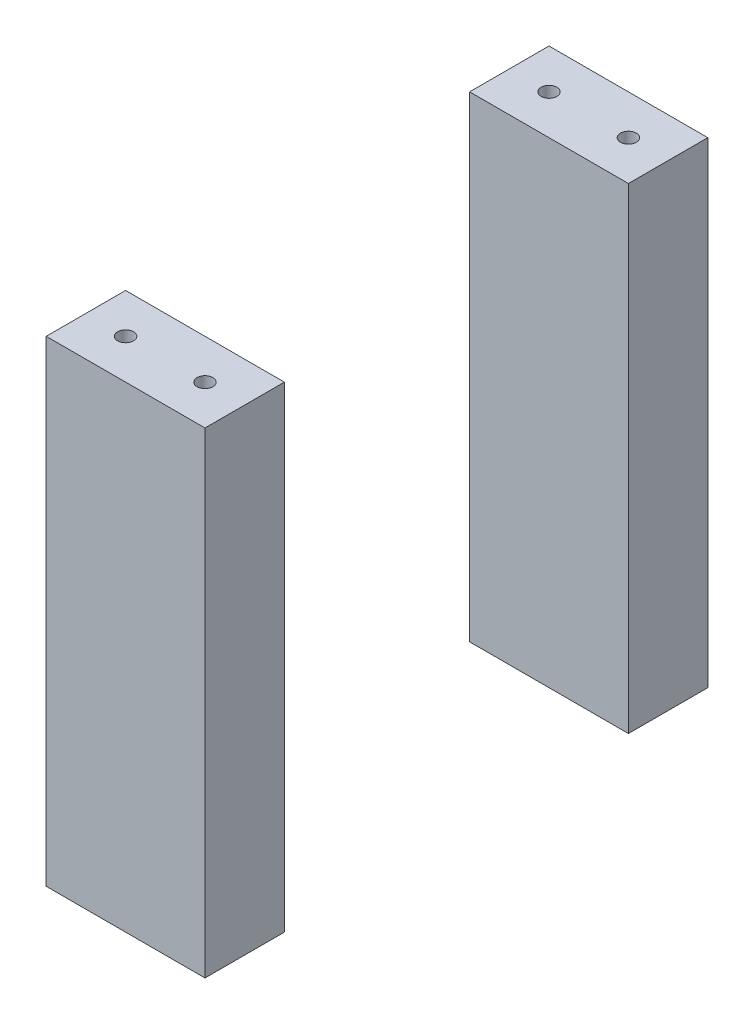
SolidWorks part; units mm, degrees
ref_plane "Ebene vorne" through (0, 0, 0) normal (0, 0, 1) x (1, 0, 0)
ref_plane "Ebene oben" through (0, 0, 0) normal (0, 1, 0) x (1, 0, 0)
ref_plane "Ebene rechts" through (0, 0, 0) normal (1, 0, 0) x (0, 0, -1)
sketch "OutlineBase" plane through (0, 0, 0) normal (0, 1, 0) x (1, 0, 0)
  line L0 (0, -95) -> (0, -285) construction
  line L1 (55, -285) -> (55, -95)
  line L2 (55, -285) -> (-55, -285)
  line L3 (-55, -285) -> (-55, -95)
  line L4 (55, -95) -> (-55, -95)
  line L5 (55, -285) -> (-55, -95) construction
  line L6 (-55, -285) -> (55, -95) construction
  line L16 (0, -190) -> (0, -150.9424) construction
  line L27 (-30, -285) -> (-30, -255)
  line L28 (-30, -285) -> (30, -285)
  line L29 (30, -285) -> (30, -255)
  line L30 (-30, -255) -> (30, -255)
  line L31 (0, -255) -> (-30, -255)
  line L32 (30, -255) -> (-30, -255)
  line L34 (30, -285) -> (-30, -285)
  line L35 (0, -190) -> (89.9295, -190) construction
  line L36 (30, -95) -> (-30, -95)
  line L39 (0, -125) -> (-30, -125)
  line L40 (-30, -125) -> (30, -125)
  line L41 (30, -95) -> (30, -125)
  line L42 (-30, -95) -> (30, -95)
  line L43 (-30, -95) -> (-30, -125)
  circle A0 centre (-15, -270) radius 3
  circle A1 centre (15, -270) radius 3
  circle A4 centre (15, -270) radius 3
  circle A5 centre (-15, -270) radius 3
  circle A6 centre (-15, -110) radius 3
  circle A7 centre (15, -110) radius 3
  circle A8 centre (15, -110) radius 3
  circle A9 centre (-15, -110) radius 3
  point P33 (0, -190)
sketch "GroundHeight" plane through (0, 0, 0) normal (0, 0, 1) x (1, 0, 0)
  line L1 (-150, -16) -> (150, -16)
  line L2 (-150, -16) -> (-150, -21)
  line L3 (-150, -21) -> (150, -21)
  line L4 (150, -16) -> (150, -21)
sketch "BaseWormGearHeight" plane through (0, 0, 0) normal (1, 0, 0) x (0, 0, -1)
  line L1 (-95, 170) -> (-285, 170)
  line L2 (-95, 170) -> (-95, 164)
  line L3 (-95, 164) -> (-285, 164)
  line L4 (-285, 170) -> (-285, 164)
  line L5 (-190, 170) -> (-190, 212) construction
  line L6 (0, 218) -> (0, 227) construction
  line L8 (-190, 212) -> (-190, 217) construction
  line L9 (-190, 217) -> (-190, 227) construction
  point P4 (-190, 164)
sketch "Skizze4" plane through (0, 0, 0) normal (0, 1, 0) x (1, 0, 0)
  line L1 (-30, -95) -> (30, -95)
  line L2 (-30, -95) -> (-30, -125)
  line L3 (-30, -125) -> (30, -125)
  line L4 (30, -95) -> (30, -125)
  line L5 (-30, -255) -> (30, -255)
  line L6 (-30, -255) -> (-30, -285)
  line L7 (-30, -285) -> (30, -285)
  line L8 (30, -255) -> (30, -285)
  circle A0 centre (-15, -110) radius 3
  circle A1 centre (15, -110) radius 3
  circle A2 centre (15, -270) radius 3
  circle A3 centre (-15, -270) radius 3
sketch "Skizze5" plane through (0, 0, 0) normal (1, 0, 0) x (0, 0, -1)
  point P0 (-95, 164)
extrude "Aufsatz-Linear austragen1" add sketch "Skizze4" along normal up to vertex (164 mm away) and the other way up to vertex (16 mm away) up to point (0, 164, 95) other way up to point (150, -16, 0)
